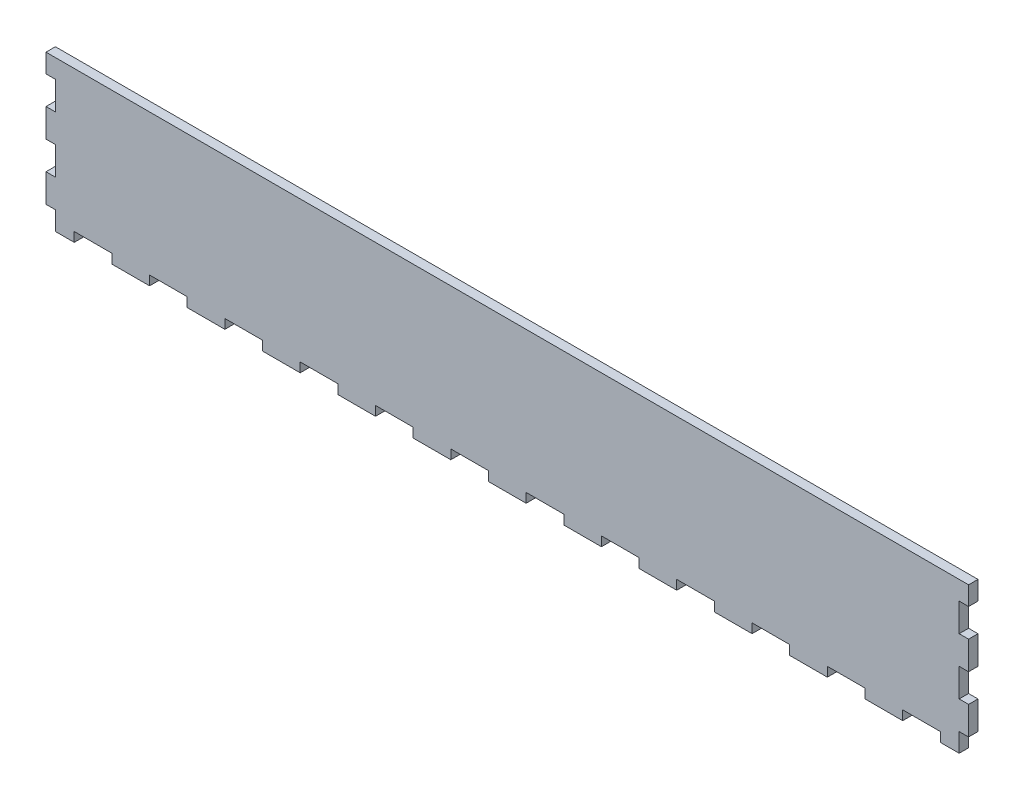
SolidWorks part; units mm, degrees
material "Oak"
ref_plane "Front Plane" through (0, 0, 0) normal (0, 0, 1) x (1, 0, 0)
ref_plane "Top Plane" through (0, 0, 0) normal (0, 1, 0) x (1, 0, 0)
ref_plane "Right Plane" through (0, 0, 0) normal (1, 0, 0) x (0, 0, -1)
sketch "Sketch2" plane through (0, 0, 0) normal (0, 0, 1) x (1, 0, 0)
  line L0 (-311.15, 38.1) -> (-304.8, 38.1)
  line L1 (-304.8, -50.8) -> (-292.1, -50.8)
  line L2 (-311.15, -38.1) -> (-311.15, -19.05)
  line L3 (-311.15, 50.8) -> (311.15, 50.8)
  line L5 (-311.15, -50.8) -> (311.15, 50.8) construction
  line L6 (-311.15, 50.8) -> (311.15, -50.8) construction
  line L7 (-304.8, 38.1) -> (-304.8, 19.05)
  line L8 (-304.8, 19.05) -> (-311.15, 19.05)
  line L9 (-311.15, 38.1) -> (-311.15, 50.8)
  line L10 (-311.15, 0) -> (-304.8, 0)
  line L11 (-304.8, 0) -> (-304.8, -19.05)
  line L12 (-304.8, -19.05) -> (-311.15, -19.05)
  line L13 (-311.15, -38.1) -> (-304.8, -38.1)
  line L14 (-304.8, -38.1) -> (-304.8, -50.8)
  line L15 (-311.15, 0) -> (-311.15, 19.05)
  line L16 (0, -55.88) -> (0, 55.88) construction
  line L17 (311.15, 0) -> (311.15, 19.05)
  line L18 (304.8, -38.1) -> (304.8, -50.8)
  line L19 (311.15, -38.1) -> (304.8, -38.1)
  line L20 (304.8, -19.05) -> (311.15, -19.05)
  line L21 (304.8, 0) -> (304.8, -19.05)
  line L22 (311.15, 0) -> (304.8, 0)
  line L23 (311.15, 38.1) -> (311.15, 50.8)
  line L24 (304.8, 19.05) -> (311.15, 19.05)
  line L25 (304.8, 38.1) -> (304.8, 19.05)
  line L26 (311.15, -38.1) -> (311.15, -19.05)
  line L27 (311.15, 38.1) -> (304.8, 38.1)
  line L28 (-292.1, -50.8) -> (-292.1, -44.45)
  line L29 (-292.1, -44.45) -> (-266.7, -44.45)
  line L30 (-266.7, -44.45) -> (-266.7, -50.8)
  line L31 (-266.7, -50.8) -> (-241.3, -50.8)
  line L32 (-241.3, -50.8) -> (-241.3, -44.45)
  line L33 (-241.3, -44.45) -> (-215.9, -44.45)
  line L34 (-215.9, -44.45) -> (-215.9, -50.8)
  line L35 (-190.5, -50.8) -> (-190.5, -44.45)
  line L36 (-190.5, -44.45) -> (-165.1, -44.45)
  line L37 (-165.1, -44.45) -> (-165.1, -50.8)
  line L38 (-139.7, -50.8) -> (-139.7, -44.45)
  line L39 (-139.7, -44.45) -> (-114.3, -44.45)
  line L40 (-114.3, -44.45) -> (-114.3, -50.8)
  line L41 (-88.9, -50.8) -> (-88.9, -44.45)
  line L42 (-88.9, -44.45) -> (-63.5, -44.45)
  line L43 (-63.5, -44.45) -> (-63.5, -50.8)
  line L44 (-38.1, -50.8) -> (-38.1, -44.45)
  line L45 (-38.1, -44.45) -> (-12.7, -44.45)
  line L46 (-12.7, -44.45) -> (-12.7, -50.8)
  line L47 (12.7, -50.8) -> (12.7, -44.45)
  line L48 (12.7, -44.45) -> (38.1, -44.45)
  line L49 (38.1, -44.45) -> (38.1, -50.8)
  line L50 (63.5, -50.8) -> (63.5, -44.45)
  line L51 (63.5, -44.45) -> (88.9, -44.45)
  line L52 (88.9, -44.45) -> (88.9, -50.8)
  line L53 (114.3, -50.8) -> (114.3, -44.45)
  line L54 (114.3, -44.45) -> (139.7, -44.45)
  line L55 (139.7, -44.45) -> (139.7, -50.8)
  line L56 (165.1, -50.8) -> (165.1, -44.45)
  line L57 (165.1, -44.45) -> (190.5, -44.45)
  line L58 (190.5, -44.45) -> (190.5, -50.8)
  line L59 (215.9, -50.8) -> (215.9, -44.45)
  line L60 (215.9, -44.45) -> (241.3, -44.45)
  line L61 (241.3, -44.45) -> (241.3, -50.8)
  line L62 (266.7, -50.8) -> (266.7, -44.45)
  line L63 (266.7, -44.45) -> (292.1, -44.45)
  line L64 (292.1, -44.45) -> (292.1, -50.8)
  line L65 (-215.9, -50.8) -> (-190.5, -50.8)
  line L66 (-165.1, -50.8) -> (-139.7, -50.8)
  line L67 (-114.3, -50.8) -> (-88.9, -50.8)
  line L68 (-63.5, -50.8) -> (-38.1, -50.8)
  line L69 (-12.7, -50.8) -> (12.7, -50.8)
  line L70 (38.1, -50.8) -> (63.5, -50.8)
  line L71 (88.9, -50.8) -> (114.3, -50.8)
  line L72 (139.7, -50.8) -> (165.1, -50.8)
  line L73 (190.5, -50.8) -> (215.9, -50.8)
  line L74 (241.3, -50.8) -> (266.7, -50.8)
  line L75 (292.1, -50.8) -> (304.8, -50.8)
  point P0 (0, 0)
  dimension "D1" = 12.7
  dimension "D2" = 101.6
  dimension "D3" = 6.35
  dimension "D4" = 19.05
  dimension "D5" = 19.05
  dimension "D6" = 19.05
  dimension "D7" = 19.05
  dimension "D8" = 25.4
  dimension "D9" = 622.3
  dimension "D10" = 6.35
  dimension "D11" = 12.7
  dimension "D13" = 25.4
  dimension "D12" = 12
extrude "Boss-Extrude1" add sketch "Sketch2" along normal blind 6.35
sketch "Sketch3" plane through (0, 0, 0) normal (0, 0, -1) x (-1, 0, 0)
  line L0 (-311.15, 0) -> (311.15, 0) construction
  text T0 "RAWB | RAWB Assists With Balancing\r\nAllen, Josh, Leo, Rajiv, MPC Lab" font "Century Gothic" height 12.7
  point P3 (-225.1592, 0)
  point P4 (311.15, 0)
extrude "Cut-Extrude1" cut sketch "Sketch3" against normal blind 1.27
